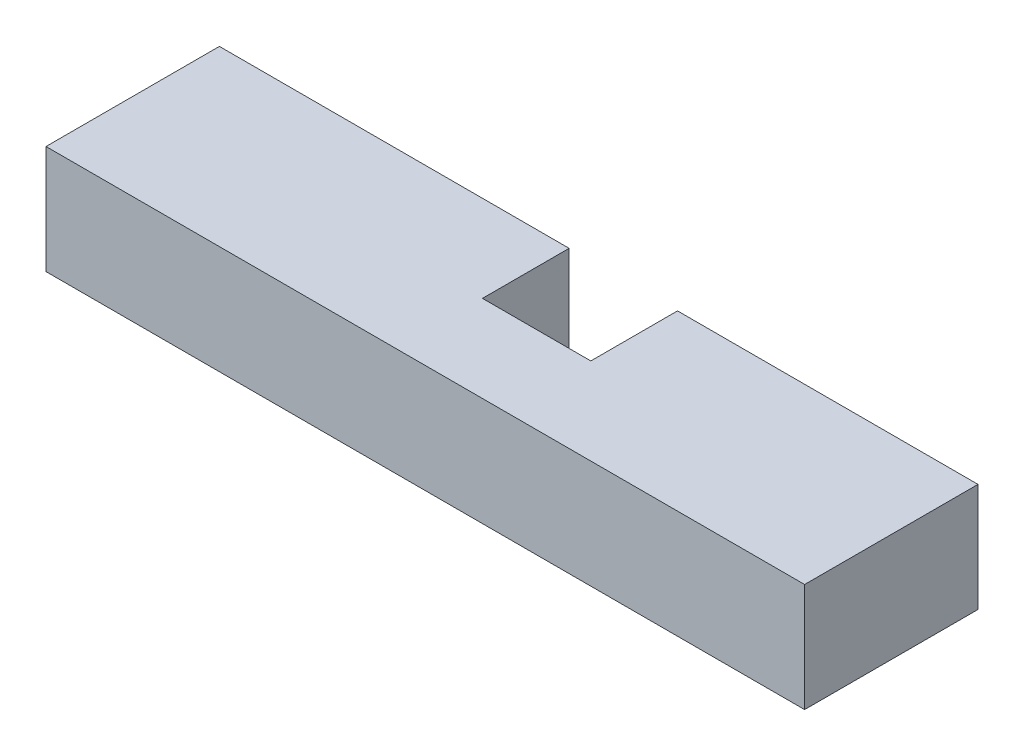
SolidWorks part; units mm, degrees
ref_plane "Front Plane" through (0, 0, 0) normal (0, 0, 1) x (1, 0, 0)
ref_plane "Top Plane" through (0, 0, 0) normal (0, 1, 0) x (1, 0, 0)
ref_plane "Right Plane" through (0, 0, 0) normal (1, 0, 0) x (0, 0, -1)
sketch "Elevator Paddle Support Strut" plane through (0, 0, 0) normal (0, 1, 0) x (1, 0, 0)
  line L0 (0, -5.08) -> (0, 0) construction
  line L1 (-22.225, -5.08) -> (22.225, -5.08)
  line L2 (-22.225, -5.08) -> (-22.225, 5.08)
  line L3 (-22.225, 5.08) -> (-1.7321, 5.08)
  line L4 (22.225, -5.08) -> (22.225, 5.08)
  line L5 (-22.225, -5.08) -> (0, 0) construction
  line L6 (-22.225, 5.08) -> (-1.7321, 0.3959) construction
  line L7 (-22.225, 0) -> (22.225, 0) construction
  line L8 (-1.7321, 0) -> (4.6179, 0)
  line L9 (-1.7321, 0) -> (-1.7321, 5.08)
  line L10 (4.6179, 1.0555) -> (22.225, 5.08) construction
  line L11 (4.6179, 0) -> (4.6179, 5.08)
  line L13 (0, 0) -> (22.225, -5.08) construction
  line L14 (4.6179, 5.08) -> (22.225, 5.08)
  point P0 (0, 0)
  dimension "D1" = 10.16
  dimension "D2" = 44.45
  dimension "D3" = 6.35
extrude "Boss-Extrude1" add sketch "Elevator Paddle Support Strut" along normal blind 6.35 contours L11 L8 L9 L3 L2 L1 L4 region at (-0.111, 0, 0.1954)
equation "\"Ball Diameter\"= 1.75in"
equation "\"Sheet Thickness\"= 0.25in"
equation "\"Screw Diameter\"= .17in"
equation "\"Robot Diameter\"= 16in"
equation "\"Castor Screw Diameter\"= 0.22in"
equation "\"Wheel Diameter\"= 4in"
equation "\"Nut Diameter\"= 8.4mm"
equation "\"Nut Height\"= 2.9mm"
equation "\"Screw Height\"= 0.55in"
equation "\"D2@Elevator Paddle Support Strut\"=\"Ball Diameter\""
equation "\"D3@Elevator Paddle Support Strut\"=\"Sheet Thickness\""
equation "\"D1@Boss-Extrude1\"=\"Sheet Thickness\""
